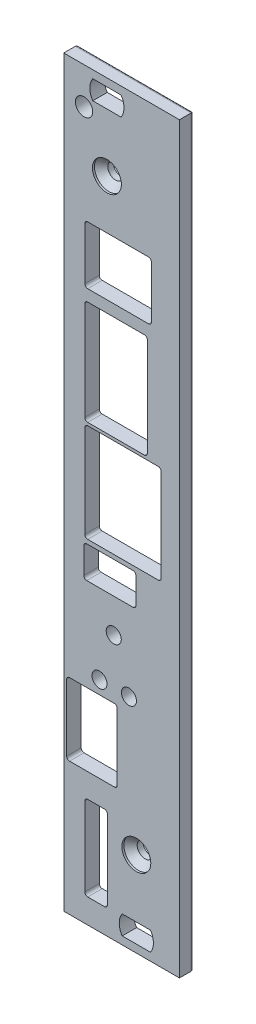
SolidWorks part; units mm, degrees
ref_plane "Front Plane" through (0, 0, 0) normal (0, 0, 1) x (1, 0, 0)
ref_plane "Top Plane" through (0, 0, 0) normal (0, 1, 0) x (1, 0, 0)
ref_plane "Right Plane" through (0, 0, 0) normal (1, 0, 0) x (0, 0, -1)
ref_plane "Plane1" through (0, 0, 2.5) normal (0, 0, 1) x (1, 0, 0)
sketch "Sketch1" plane through (0, 0, 2.5) normal (0, 0, 1) x (1, 0, 0)
  line L0 (12.53, 125.4) -> (-7.45, 125.4)
  line L1 (-7.45, 125.4) -> (-7.45, -3)
  line L2 (-7.45, -3) -> (12.53, -3)
  line L3 (12.53, -3) -> (12.53, 125.4)
extrude "Boss-Extrude1" add sketch "Sketch1" against normal blind 2.5
sketch "Sketch2" plane through (0, 0, 2.5) normal (0, 0, 1) x (1, 0, 0)
  line L0 (2.4454, 124.05) -> (-2.4454, 124.05)
  line L1 (-2.4454, 120.75) -> (2.4454, 120.75)
  arc A0 (-2.4454, 124.05) -> (-2.4454, 120.75) centre (0, 122.4) ccw
  arc A1 (2.4454, 120.75) -> (2.4454, 124.05) centre (0, 122.4) ccw
extrude "Cut-Extrude1" cut sketch "Sketch2" against normal through all
sketch "Sketch3" plane through (0, 0, 2.5) normal (0, 0, 1) x (1, 0, 0)
  line L0 (7.5254, 1.65) -> (2.6346, 1.65)
  line L1 (2.6346, -1.65) -> (7.5254, -1.65)
  arc A0 (2.6346, 1.65) -> (2.6346, -1.65) centre (5.08, 0) ccw
  arc A1 (7.5254, -1.65) -> (7.5254, 1.65) centre (5.08, 0) ccw
extrude "Cut-Extrude2" cut sketch "Sketch3" against normal through all
sketch "Sketch4" plane through (0, 0, 0) normal (0, 0, -1) x (-1, 0, 0)
  line L0 (3.82, 15.8) -> (-0.08, 15.8)
  line L1 (-0.08, 15.8) -> (-0.08, 1.2)
  line L2 (-0.08, 1.2) -> (3.82, 1.2)
  line L3 (3.82, 1.2) -> (3.82, 15.8)
extrude "Cut-Extrude3" cut sketch "Sketch4" against normal through all
hole_wizard "Ø3.0 (3) Diameter Hole1" positions "Sketch6" profile "Sketch5" hole size "Ø3.0" standard "ANSI Metric"
sketch "Sketch6" plane through (0, 0, 2.5) normal (0, 0, 1) x (1, 0, 0)
  point P0 (-3.95, 119.1)
sketch "Sketch5" plane through (-3.95, 119.1, 2.5) normal (1, 0, 0) x (0, -1, 0)
  line L0 (0, 0) -> (0, 2.5)
  line L1 (0, 2.5) -> (1.5, 2.5)
  line L2 (1.5, 2.5) -> (1.5, 0)
  line L5 (1.5, 0) -> (0, 0)
  line L11 (0, -6.35) -> (0, 107.95) construction
  dimension "Thru Hole Dia." = 3
  dimension "Thru Hole Depth" = 2.5
hole_wizard "CSK for M2.5 Flat Head Machine Screw1" positions "Sketch8" profile "Sketch7" countersink size "M2.5" standard "ANSI Metric"
sketch "Sketch8" plane through (0, 0, 2.5) normal (0, 0, 1) x (1, 0, 0)
  point P0 (5.08, 11.7)
  point P1 (0, 110.7)
sketch "Sketch7" plane through (5.08, 11.7, 2.5) normal (1, 0, 0) x (0, -1, 0)
  line L0 (0, 0) -> (0, 2.5)
  line L1 (0, 2.5) -> (1.35, 2.5)
  line L2 (1.35, 2.5) -> (1.35, 1.5)
  line L3 (1.35, 1.5) -> (2.5, 0.35)
  line L4 (2.5, 0.35) -> (2.5, 0)
  line L6 (2.5, 0) -> (0, 0)
  line L7 (-1.35, 1.5) -> (-2.5, 0.35) construction
  line L11 (0, -6.35) -> (0, 107.95) construction
  dimension "Thru Hole Dia." = 2.7
  dimension "Thru Hole Depth" = 2.5
  dimension "C'Sink Dia." = 5
  dimension "C'Sink Angle" = 90
  dimension "Head Clearance" = 0.35
ref_plane "Board bottom" through (0, 11.2, 0) normal (0, -1, 0) x (-1, 0, 0)
ref_plane "Board top" through (0, 111.2, 0) normal (0, 1, 0) x (1, 0, 0)
ref_plane "Board upper surface" through (-3.82, 0, 0) normal (1, 0, 0) x (0, 0, -1)
ref_plane "Board lower surface" through (-5.42, 0, 0) normal (1, 0, 0) x (0, 0, -1)
sketch "Sketch9" plane through (0, 0, 2.5) normal (0, 0, 1) x (1, 0, 0)
  line L0 (-3.82, 19.95) -> (-3.82, 32.45) construction
  line L1 (-3.82, 19.95) -> (1.78, 19.95)
  line L2 (-3.82, 32.45) -> (1.78, 32.45)
  line L3 (1.78, 19.95) -> (1.78, 32.45)
  line L4 (-3.82, -47.3899) -> (-3.82, 47.3899) construction
  line L5 (-28.8918, 11.2) -> (28.8918, 11.2) construction
  line L6 (-3.82, 32.45) -> (-3.82, 19.95) construction
  line L7 (-3.82, 32.45) -> (-6.95, 32.45)
  line L8 (-3.82, 19.95) -> (-6.95, 19.95)
  line L9 (-6.95, 32.45) -> (-6.95, 19.95)
  line L10 (-6.95, 32.45) -> (1.78, 19.95) construction
  line L11 (1.78, 32.45) -> (-6.95, 19.95) construction
  line L12 (-7.45, 125.4) -> (-7.45, -3) construction
  point P8 (-2.585, 26.2)
  dimension "D1" = 8.75
  dimension "D2" = 21.25
  dimension "D3" = 5.6
  dimension "D4" = 3.13
  dimension "D5" = 15
  dimension "D6" = 1.235
  dimension "D7" = 12.5
  dimension "D8" = 8.73
  dimension "D9" = 0.5
extrude "USB" cut sketch "Sketch9" against normal through all
sketch "Sketch10" plane through (0, 0, 2.5) normal (0, 0, 1) x (1, 0, 0)
  line L0 (-3.82, 34.72) -> (3.8, 34.72) construction
  line L1 (-3.82, -47.3899) -> (-3.82, 47.3899) construction
  line L3 (-28.8918, 11.2) -> (28.8918, 11.2) construction
  circle A0 centre (-1.28, 34.72) radius 1.3
  circle A1 centre (3.8, 34.72) radius 1.3
  dimension "D1" = 2.6
  dimension "D2" = 2.6
  dimension "D3" = 2.54
  dimension "D4" = 5.08
  dimension "D5" = 23.52
extrude "LEDs" cut sketch "Sketch10" against normal through all
sketch "Sketch11" plane through (0, 0, 2.5) normal (0, 0, 1) x (1, 0, 0)
  line L0 (1.18, 42.62) -> (-3.82, 42.62) construction
  line L1 (-3.82, -47.3899) -> (-3.82, 47.3899) construction
  line L3 (-28.8918, 11.2) -> (28.8918, 11.2) construction
  circle A0 centre (1.18, 42.62) radius 1.3
  dimension "D1" = 2.6
  dimension "D2" = 5
  dimension "D3" = 31.42
extrude "Single LED" cut sketch "Sketch11" against normal through all
sketch "Sketch13" plane through (0, 0, 2.5) normal (0, 0, 1) x (1, 0, 0)
  line L0 (0.505, 51.2) -> (-3.82, 51.2) construction
  line L1 (-3.82, -47.3899) -> (-3.82, 47.3899) construction
  line L2 (-28.8918, 11.2) -> (28.8918, 11.2) construction
  line L4 (-3.995, 48.45) -> (5.005, 48.45)
  line L5 (-3.995, 48.45) -> (-3.995, 53.95)
  line L6 (-3.995, 53.95) -> (5.005, 53.95)
  line L7 (5.005, 48.45) -> (5.005, 53.95)
  line L8 (-3.995, 48.45) -> (5.005, 53.95) construction
  line L9 (-3.995, 53.95) -> (5.005, 48.45) construction
  point P1 (0.505, 51.2)
  dimension "D1" = 5.5
  dimension "D2" = 40
  dimension "D3" = 4.325
  dimension "D4" = 9
extrude "Disable comms" cut sketch "Sketch13" against normal through all
sketch "Sketch14" plane through (0, 0, 2.5) normal (0, 0, 1) x (1, 0, 0)
  line L0 (-3.82, 54.7) -> (-3.82, 71.7)
  line L1 (-3.82, 54.7) -> (9.38, 54.7)
  line L2 (-3.82, 71.7) -> (9.38, 71.7)
  line L3 (9.38, 54.7) -> (9.38, 71.7)
  line L4 (-3.82, -47.3899) -> (-3.82, 47.3899) construction
  line L5 (-28.8918, 11.2) -> (28.8918, 11.2) construction
  dimension "D1" = 43.5
  dimension "D2" = 60.5
  dimension "D3" = 13.2
extrude "RJ45" cut sketch "Sketch14" against normal through all
sketch "Sketch15" plane through (0, 0, 2.5) normal (0, 0, 1) x (1, 0, 0)
  line L0 (-3.82, 72.2) -> (-3.82, 90.2)
  line L1 (-3.82, 72.2) -> (6.98, 72.2)
  line L2 (-3.82, 90.2) -> (6.98, 90.2)
  line L3 (6.98, 72.2) -> (6.98, 90.2)
  line L4 (-3.82, -47.3899) -> (-3.82, 47.3899) construction
  line L5 (-28.8918, 11.2) -> (28.8918, 11.2) construction
  dimension "D1" = 61
  dimension "D2" = 79
  dimension "D3" = 10.8
extrude "Output" cut sketch "Sketch15" against normal through all
sketch "Sketch16" plane through (0, 0, 2.5) normal (0, 0, 1) x (1, 0, 0)
  line L0 (-3.82, 92.2) -> (-3.82, 102.2)
  line L1 (-3.82, 92.2) -> (7.68, 92.2)
  line L2 (-3.82, 102.2) -> (7.68, 102.2)
  line L3 (7.68, 92.2) -> (7.68, 102.2)
  line L4 (-3.82, -47.3899) -> (-3.82, 47.3899) construction
  line L5 (-28.8918, 11.2) -> (28.8918, 11.2) construction
  dimension "D1" = 81
  dimension "D2" = 91
  dimension "D3" = 11.5
extrude "Power" cut sketch "Sketch16" against normal through all
fillet "Fillets" radius 0.5 24 edges at (1.78, 19.95, 1.25) (-6.95, 19.95, 1.25) (-6.95, 32.45, 1.25) (1.78, 32.45, 1.25) (0.08, 1.2, 1.25) (-3.82, 1.2, 1.25) (-3.82, 15.8, 1.25) (0.08, 15.8, 1.25) (9.38, 71.7, 1.25) (6.98, 90.2, 1.25) (7.68, 102.2, 1.25) (-3.82, 71.7, 1.25) (-3.82, 90.2, 1.25) (-3.82, 102.2, 1.25) (-3.82, 54.7, 1.25) (-3.82, 72.2, 1.25) (-3.82, 92.2, 1.25) (9.38, 54.7, 1.25) (6.98, 72.2, 1.25) (7.68, 92.2, 1.25) (-3.995, 48.45, 1.25) (5.005, 48.45, 1.25) (5.005, 53.95, 1.25) (-3.995, 53.95, 1.25)
fillet "Fillet2" radius 0.5 4 edges at (12.53, 61.2, 0) (2.54, -3, 0) (-7.45, 61.2, 0) (2.54, 125.4, 0) type face fillet first side face at (2.54, -3, 1.25) first side face at (-7.45, 61.2, 1.25) first side face at (12.53, 61.2, 1.25) first side face at (2.54, 125.4, 1.25) second side face at (1.93, 97.2, 0)
equation "\"D6@Sketch9\"=2.47/2"
